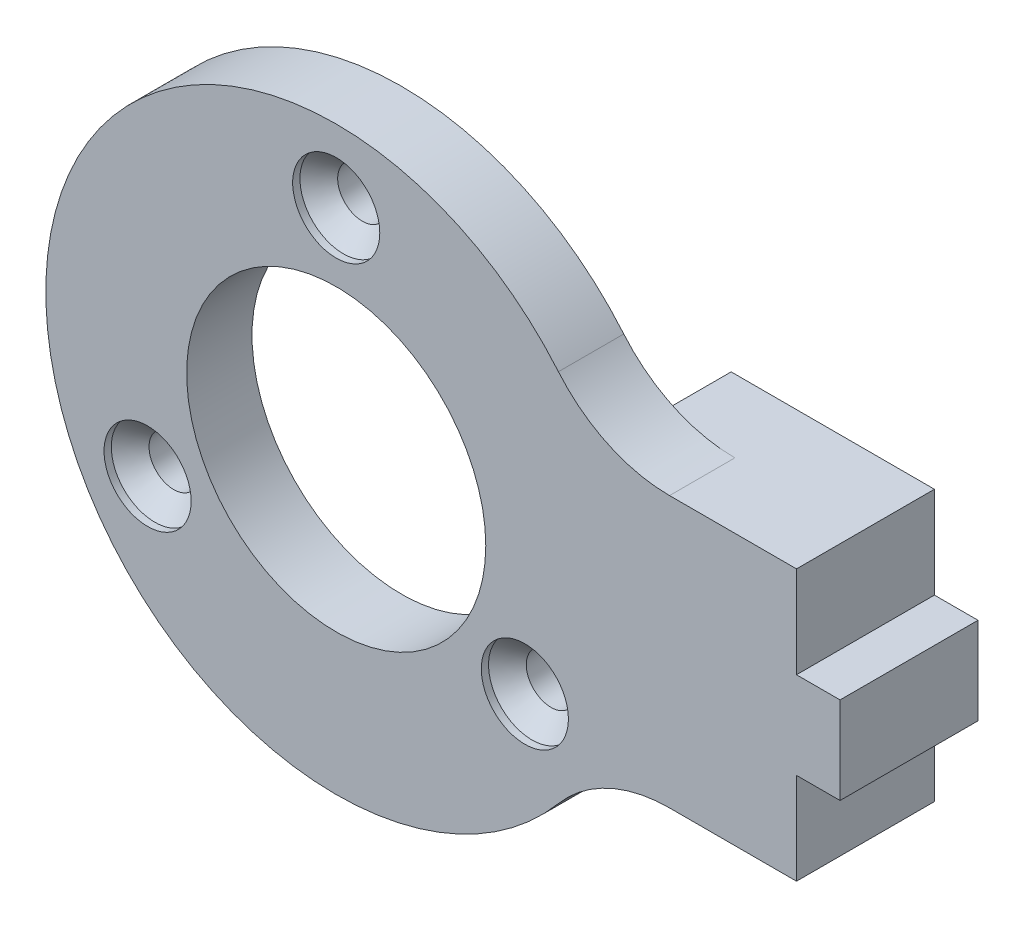
SolidWorks part; units mm, degrees
ref_plane "Alzado" through (0, 0, 0) normal (0, 0, 1) x (1, 0, 0)
ref_plane "Planta" through (0, 0, 0) normal (0, 1, 0) x (1, 0, 0)
ref_plane "Vista lateral" through (0, 0, 0) normal (1, 0, 0) x (0, 0, -1)
sketch "Croquis1" plane through (0, 0, 0) normal (0, 0, 1) x (1, 0, 0)
  line L0 (17.6984, 9.3149) -> (31.6984, 9.3149)
  line L6 (31.6984, 9.3149) -> (31.6984, -9.3149)
  line L9 (17.6984, -9.3149) -> (31.6984, -9.3149)
  circle A1 centre (0, 0) radius 10.3
  arc A3 (17.6984, 9.3149) -> (17.6984, -9.3149) centre (0, 0) ccw
  circle A4 centre (12.9904, -7.5) radius 1.7
  circle A5 centre (0, 15) radius 1.7
  circle A6 centre (-12.9904, -7.5) radius 1.7
extrude "Saliente-Extruir1" add sketch "Croquis1" along normal blind 4.5
sketch "Croquis4" plane through (0, 0, 4.5) normal (0, 0, 1) x (1, 0, 0)
  circle A0 centre (0, 15) radius 3
  circle A1 centre (12.9904, -7.5) radius 3
  circle A2 centre (-12.9904, -7.5) radius 3
extrude "Cortar-Extruir2" cut sketch "Croquis4" against normal blind 2
chamfer "Chaflán2" distance 1.5 angle 45 3 edges at (15.9904, -7.5, 2.5) (3, 15, 2.5) (-9.9904, -7.5, 2.5)
sketch "Croquis6" plane through (31.6984, 0, 0) normal (1, 0, 0) x (0, 0, -1)
  line L0 (-4.5, 0) -> (-4.5, 3)
  line L1 (-4.5, -9.3149) -> (-4.5, 9.3149) construction
  line L2 (-4.5, 3) -> (0, 3)
  line L3 (0, -9.3149) -> (0, 9.3149) construction
  line L4 (0, 3) -> (0, -3)
  line L5 (0, -3) -> (-4.5, -3)
  line L6 (-4.5, -3) -> (-4.5, 0)
extrude "Saliente-Extruir2" add sketch "Croquis6" along normal blind 3
sketch "Croquis7" plane through (0, 0, 0) normal (0, 0, -1) x (-1, 0, 0)
  line L0 (-17.6984, -9.3149) -> (-31.6984, -9.3149)
  line L1 (-31.6984, -9.3149) -> (-31.6984, -3)
  line L2 (-31.6984, -3) -> (-34.6984, -3)
  line L3 (-34.6984, -3) -> (-34.6984, 3)
  line L4 (-34.6984, 3) -> (-31.6984, 3)
  line L5 (-31.6984, 3) -> (-31.6984, 9.3149)
  line L6 (-31.6984, 9.3149) -> (-17.6984, 9.3149)
  line L7 (-17.6984, 9.3149) -> (-17.6984, -9.3149)
extrude "Saliente-Extruir3" add sketch "Croquis7" along normal blind 5
sketch "Croquis8" plane through (0, 0, -5) normal (0, 0, -1) x (-1, 0, 0)
  circle A0 centre (0, 0) radius 20
extrude "Cortar-Extruir3" cut sketch "Croquis8" against normal blind 5
fillet "Redondeo1" radius 10 2 edges at (17.6984, -9.3149, 2.25) (17.6984, 9.3149, 2.25)
